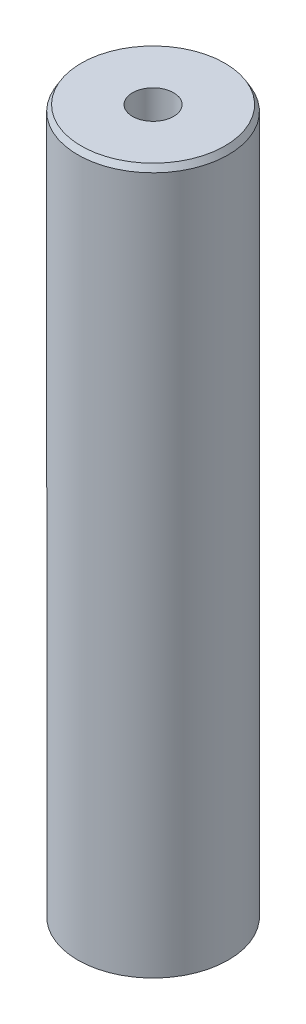
SolidWorks part; units mm, degrees
ref_plane "Front Plane" through (0, 0, 0) normal (0, 0, 1) x (1, 0, 0)
ref_plane "Top Plane" through (0, 0, 0) normal (0, 1, 0) x (1, 0, 0)
ref_plane "Right Plane" through (0, 0, 0) normal (1, 0, 0) x (0, 0, -1)
sketch "Sketch1" plane through (0, 0, 0) normal (0, 1, 0) x (1, 0, 0)
  circle A0 centre (0, 0) radius 17.5
  dimension "SHAFT_OD" = 35
extrude "Boss-Extrude1" add sketch "Sketch1" along normal blind 164.3914
sketch "Sketch2" plane through (0, 0, 0) normal (0, 1, 0) x (1, 0, 0)
  circle A0 centre (0, 0) radius 4.781
  dimension "BORE_D" = 9.562
extrude "Cut-Extrude1" cut sketch "Sketch2" along normal through all
chamfer "Chamfer1" distance 1.3801 angle 30 2 edges at (0, 164.3914, 17.5) (0, 0, 17.5) first distance on face at (0, 164.3914, 17.5) first distance on face at (0, 0, 4.781)
